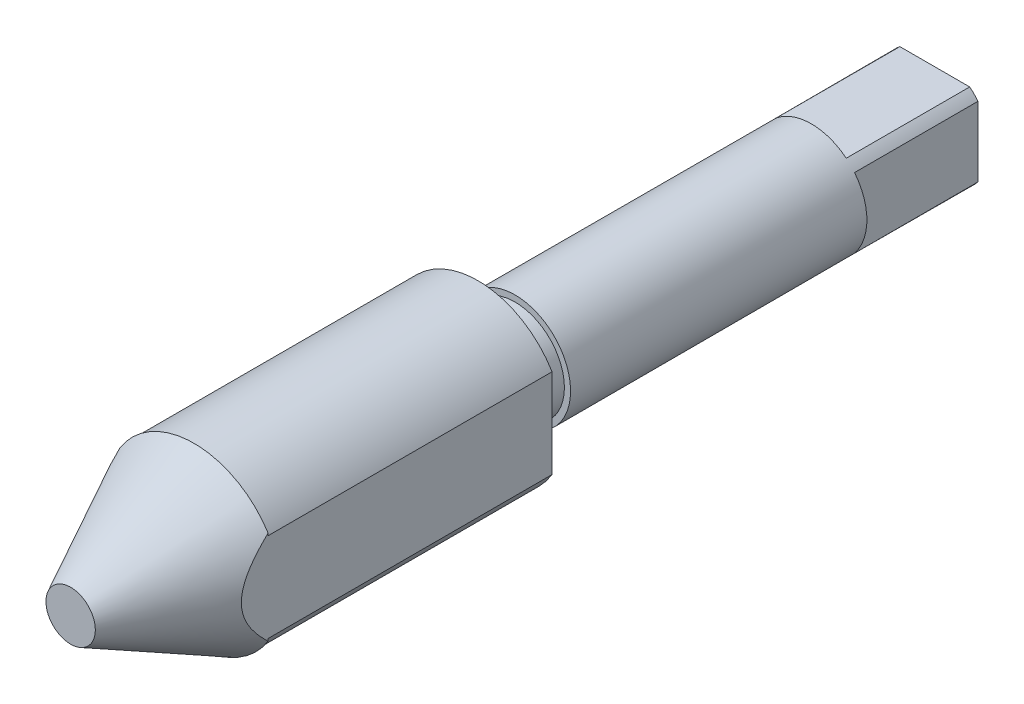
SolidWorks part; units mm, degrees
ref_plane "Спереди" through (0, 0, 0) normal (0, 0, 1) x (1, 0, 0)
ref_plane "Сверху" through (0, 0, 0) normal (0, 1, 0) x (1, 0, 0)
ref_plane "Справа" through (0, 0, 0) normal (1, 0, 0) x (0, 0, -1)
sketch "Эскиз1" plane through (0, 0, 0) normal (0, 0, 1) x (1, 0, 0)
  circle A0 centre (0, 0) radius 4.5
  dimension "D1" = 9
extrude "Бобышка-Вытянуть1" add sketch "Эскиз1" along normal blind 34
sketch "Эскиз2" plane through (0, 0, 34) normal (0, 0, 1) x (1, 0, 0)
  circle A0 centre (0, 0) radius 4
  dimension "D1" = 8
extrude "Бобышка-Вытянуть2" add sketch "Эскиз2" along normal blind 3
sketch "Эскиз3" plane through (0, 0, 37) normal (0, 0, 1) x (1, 0, 0)
  line L1 (-6, 7) -> (6, 7)
  line L2 (-6, 7) -> (-6, -7)
  line L3 (-6, -7) -> (6, -7)
  line L4 (6, 7) -> (6, -7)
  line L5 (-6, 7) -> (6, -7) construction
  line L6 (-6, -7) -> (6, 7) construction
  circle A0 centre (0, 0) radius 7
  circle M3 centre (0, 0) radius 4
  dimension "D1" = 14
  dimension "D2" = 12
  dimension "D3" = 14
extrude "Бобышка-Вытянуть3" add sketch "Эскиз3" along normal blind 23 contours L4 A0 L2 M3 | M3 region at (3.356, 5.9321, 37) region at (0, 0, 37)
sketch3d "Трехмерный эскиз1"
  circle A0 centre (0.0075, -0.0038, 70) radius 2
  point P2 (0.0075, -0.0038, 72)
  dimension "D2" = 4
  dimension "D1" = 10
extrude "Бобышка-Вытянуть4" add sketch "Трехмерный эскиз1" along direction (0, 0, 1) on the side against the normal blind 10 draft 27 contours A0 draft outward yes
sketch "Эскиз7" plane through (0, 0, 60) normal (0, 0, -1) x (-1, 0, 0)
  line L4 (-6, -4.3899) -> (-7.7962, -4.3899)
  line L7 (-6, -4.3899) -> (-6, 5.4257)
  line L8 (-6, 5.4257) -> (-7.7962, 5.4257)
  line L9 (-7.7962, -4.3899) -> (-7.7962, 5.4257)
  line L12 (6, 4.2365) -> (8.9586, 4.2365)
  line L15 (6, 4.2365) -> (6, -6.6035)
  line L16 (6, -6.6035) -> (8.9586, -6.6035)
  line L17 (8.9586, 4.2365) -> (8.9586, -6.6035)
extrude "Вырез-Вытянуть14" cut sketch "Эскиз7" against normal blind 4
hole_wizard "Сверло под метчик  спиральное M53" positions "Эскиз14" profile "Эскиз15" hole size "M5x0.8" standard "DIN"
sketch "Эскиз14" plane through (0, 0, 0) normal (0, 0, -1) x (-1, 0, 0)
  point P0 (0, 0)
sketch "Эскиз15" plane through (0, 0, 0) normal (1, 0, 0) x (0, 1, 0)
  line L0 (0, 0) -> (0, 14.5622)
  line L1 (0, 14.5622) -> (2.6, 13)
  line L2 (2.6, 13) -> (2.6, 0)
  line L5 (2.6, 0) -> (0, 0)
  line L10 (0, 14.5622) -> (-2.6, 13) construction
  line L11 (0, -6.35) -> (0, 107.95) construction
  dimension "Диаметр отверстия" = 5.2
  dimension "Глубина отверстия" = 13
  dimension "Угол заточки сверла" = 118
sketch "Эскиз16" plane through (0, 0, 0) normal (0, 0, -1) x (-1, 0, 0)
  line L1 (-3.5, -3.5) -> (3.5, -3.5)
  line L2 (-3.5, -3.5) -> (-3.5, 3.5)
  line L3 (-3.5, 3.5) -> (3.5, 3.5)
  line L4 (3.5, -3.5) -> (3.5, 3.5)
  line L5 (-3.5, -3.5) -> (3.5, 3.5) construction
  line L6 (-3.5, 3.5) -> (3.5, -3.5) construction
  circle A0 centre (0, 0) radius 10.3467
  point P0 (0, 0)
  dimension "D1" = 7
  dimension "D2" = 7
extrude "Вырез-Вытянуть15" cut sketch "Эскиз16" against normal blind 10
